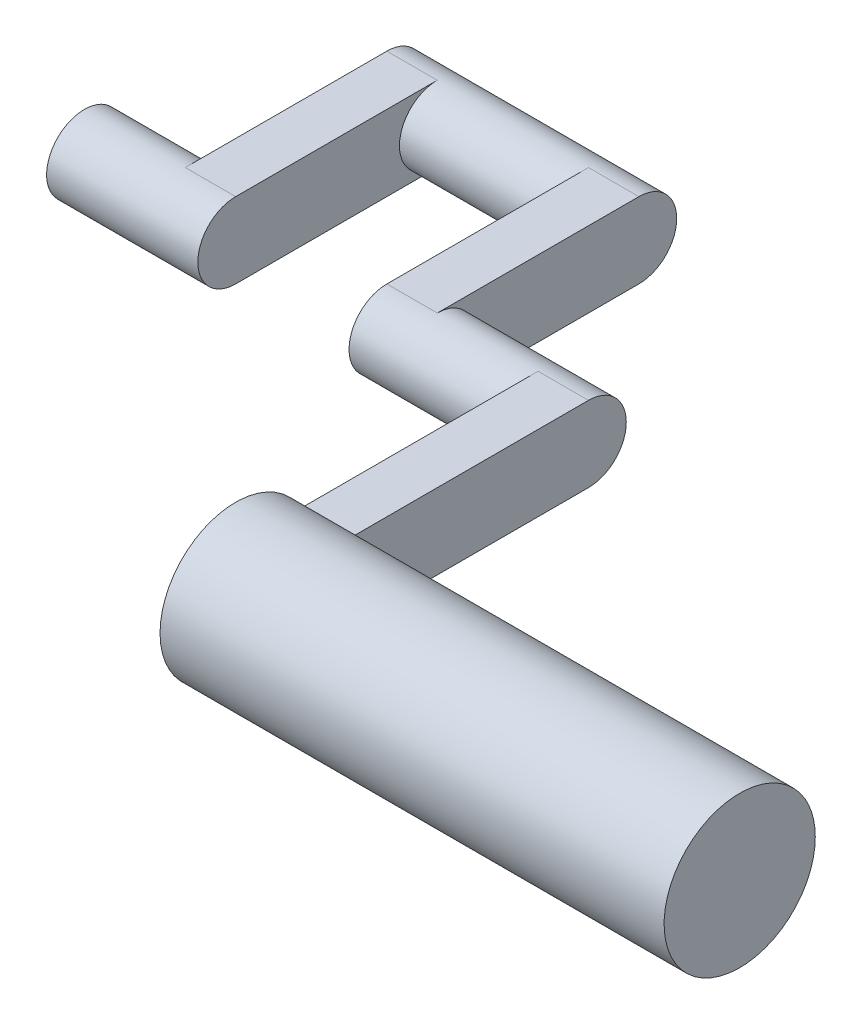
SolidWorks part; units mm, degrees
ref_plane "Front Plane" through (0, 0, 0) normal (0, 0, 1) x (1, 0, 0)
ref_plane "Top Plane" through (0, 0, 0) normal (0, 1, 0) x (1, 0, 0)
ref_plane "Right Plane" through (0, 0, 0) normal (1, 0, 0) x (0, 0, -1)
sketch "Sketch1" plane through (0, 0, 0) normal (1, 0, 0) x (0, 0, -1)
  line L0 (127, 9.525) -> (16.4978, 9.525)
  line L1 (127, -9.525) -> (16.4978, -9.525)
  circle A0 centre (0, 0) radius 19.05
  circle A1 centre (76.2, 0) radius 9.525
  circle A2 centre (127, 0) radius 9.525
  dimension "D1" = 38.1
  dimension "D4" = 19.05
  dimension "D2" = 76.2
  dimension "D3" = 50.8
extrude "Boss-Extrude1" add sketch "Sketch1" along normal blind 127 contours A0 region at (0, 0, 0)
extrude "Boss-Extrude2" add sketch "Sketch1<3>" along normal blind 12.7 contours A1 L0 A0 L1 region at (0, 0, -43.5104)
sketch "Sketch1<3>" plane through (0, 0, 0) normal (1, 0, 0) x (0, 0, -1) same geometry as "Sketch1"
extrude "Boss-Extrude3" add sketch "Sketch1<4>" along normal blind 12.7 and the other way blind 38.1 contours A1 region at (0, 0, -76.2)
sketch "Sketch1<4>" plane through (0, 0, 0) normal (1, 0, 0) x (0, 0, -1) same geometry as "Sketch1"
extrude "Boss-Extrude4" add sketch "Sketch1<5>" along normal blind 12.7 from offset 38.1 contours A2 L0 A1 L1 region at (0, 0, -101.6) offset against normal yes
sketch "Sketch1<5>" plane through (0, 0, 0) normal (1, 0, 0) x (0, 0, -1) same geometry as "Sketch1"
extrude "Boss-Extrude5" add sketch "Sketch1<6>" against normal blind 63.5 from offset 25.4 contours A2 region at (0, 0, -127) offset against normal yes
sketch "Sketch1<6>" plane through (0, 0, 0) normal (1, 0, 0) x (0, 0, -1) same geometry as "Sketch1"
extrude "Boss-Extrude6" add sketch "Sketch1<7>" along normal blind 12.7 from offset 88.9 contours A2 L0 A1 L1 region at (0, 0, -101.6) offset against normal yes
sketch "Sketch1<7>" plane through (0, 0, 0) normal (1, 0, 0) x (0, 0, -1) same geometry as "Sketch1"
extrude "Boss-Extrude7" add sketch "Sketch1<8>" against normal blind 38.1 from offset 76.2 contours A1 offset against normal yes
sketch "Sketch1<8>" plane through (0, 0, 0) normal (1, 0, 0) x (0, 0, -1) same geometry as "Sketch1"
